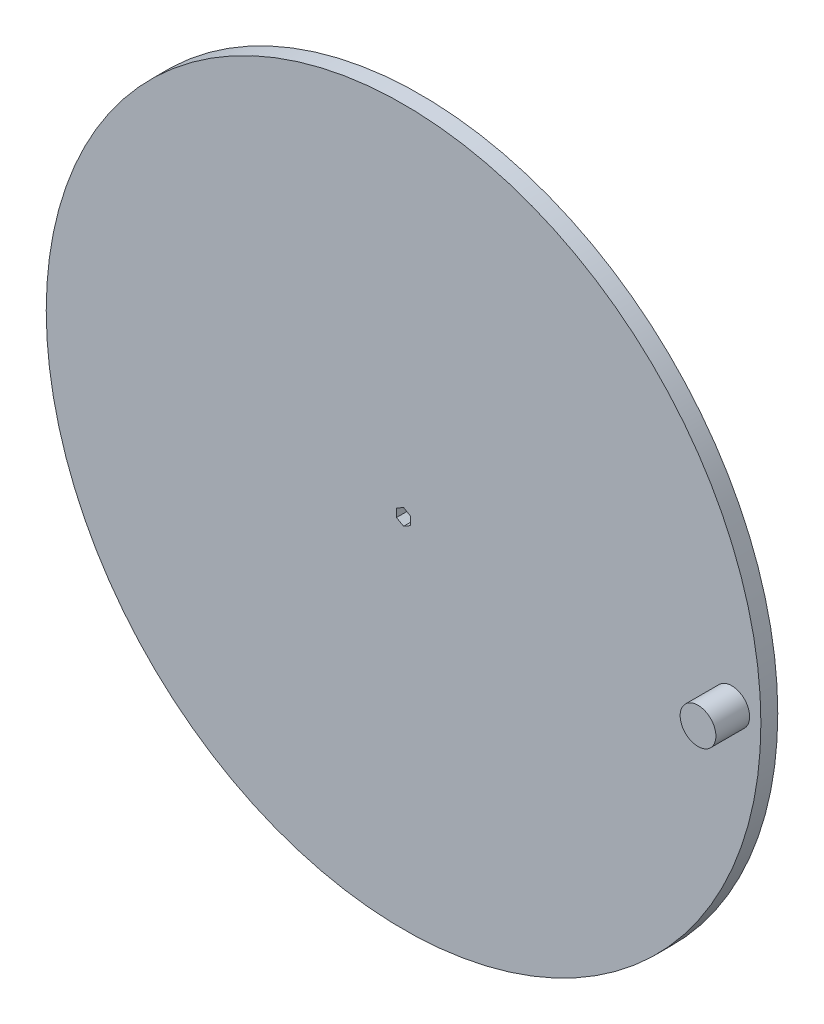
SolidWorks part; units mm, degrees
ref_plane "Front Plane" through (0, 0, 0) normal (0, 0, 1) x (1, 0, 0)
ref_plane "Top Plane" through (0, 0, 0) normal (0, 1, 0) x (1, 0, 0)
ref_plane "Right Plane" through (0, 0, 0) normal (1, 0, 0) x (0, 0, -1)
sketch "Sketch1" plane through (0, 0, 0) normal (0, 0, 1) x (1, 0, 0)
  circle A0 centre (0, 0) radius 63.5
extrude "Boss-Extrude1" add sketch "Sketch1" along normal blind 3
sketch "Sketch3" plane through (0, 0, 3) normal (0, 0, 1) x (1, 0, 0)
  circle A3 centre (58.325, 0) radius 3.175
extrude "Boss-Extrude2" add sketch "Sketch3" along normal blind 6
sketch "Sketch4" plane through (0, 0, 3) normal (0, 0, 1) x (1, 0, 0)
  line L1 (0, 1.4434) -> (-1.25, 0.7217)
  line L2 (-1.25, 0.7217) -> (-1.25, -0.7217)
  line L3 (-1.25, -0.7217) -> (0, -1.4434)
  line L4 (0, -1.4434) -> (1.25, -0.7217)
  line L5 (1.25, -0.7217) -> (1.25, 0.7217)
  line L6 (1.25, 0.7217) -> (0, 1.4434)
  circle A0 centre (0, 0) radius 1.25 construction
  dimension "D1" = 2.5
extrude "Cut-Extrude1" cut sketch "Sketch4" against normal blind 6
sketch "Sketch5" plane through (0, 0, 0) normal (0, 0, -1) x (-1, 0, 0)
  line L0 (-1.25, 0.7217) -> (0, 1.4434)
  line L1 (0, 1.4434) -> (1.25, 0.7217)
  line L2 (1.25, 0.7217) -> (1.25, -0.7217)
  line L3 (1.25, -0.7217) -> (0, -1.4434)
  line L4 (1.25, -0.7217) -> (0, -1.4434) construction
  line L5 (0, -1.4434) -> (-1.25, -0.7217)
  line L6 (-1.25, -0.7217) -> (-1.25, 0.7217)
  circle A0 centre (0, 0) radius 2.5
extrude "Boss-Extrude3" add sketch "Sketch5" along normal blind 6.5
fillet "Fillet1" radius 10 1 edges at (2.5, 0, 0)
